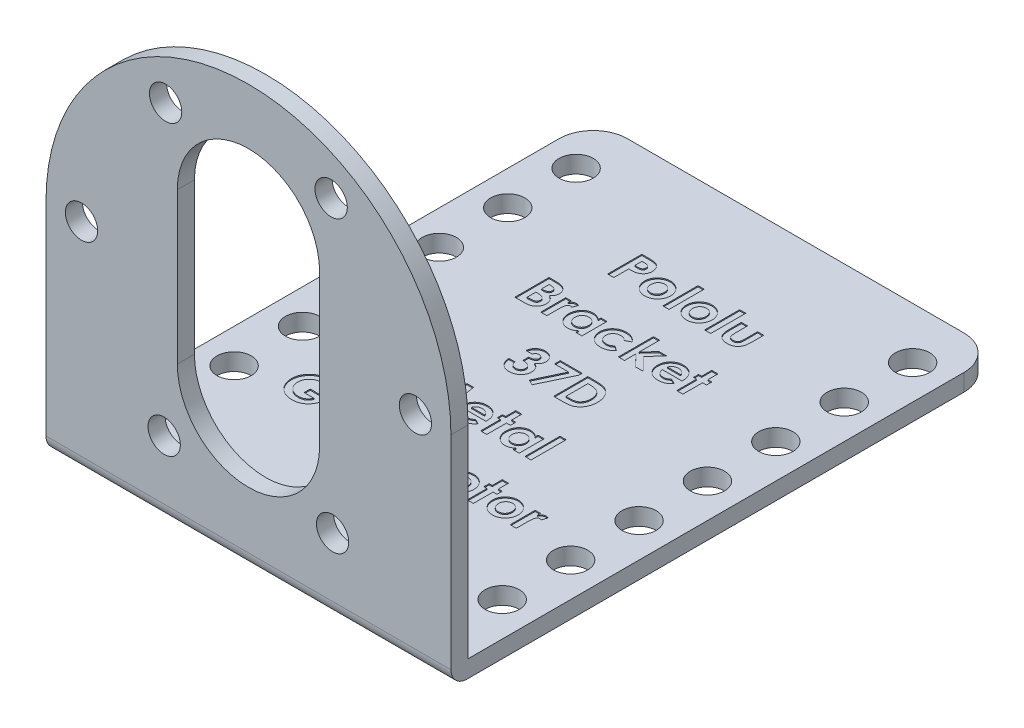
SolidWorks part; units mm, degrees
ref_plane "Plan de face" through (0, 0, 0) normal (0, 0, 1) x (1, 0, 0)
ref_plane "Plan de dessus" through (0, 0, 0) normal (0, 1, 0) x (1, 0, 0)
ref_plane "Plan de droite" through (0, 0, 0) normal (1, 0, 0) x (0, 0, -1)
sketch "Esquisse1" plane through (0, 0, 0) normal (1, 0, 0) x (0, 0, -1)
  line L2 (0, 0) -> (0, 39.18)
  line L3 (0, 39.18) -> (1.59, 39.18)
  line L4 (1.59, 1.59) -> (1.59, 39.18)
  line L5 (0, 0) -> (50.8, 0)
  line L7 (1.59, 1.59) -> (50.8, 1.59)
  line L8 (50.8, 0) -> (50.8, 1.59)
  dimension "D1" = 1.59
  dimension "D2" = 1.59
  dimension "D3" = 39.18
  dimension "D4" = 50.8
extrude "Boss.-Extru.1" add sketch "Esquisse1" along normal blind 37.59
sketch "Esquisse2" plane through (0, 0, 0) normal (0, 0, 1) x (1, 0, 0)
  line L0 (0, 39.18) -> (0, 0) construction
  line L1 (37.59, 39.18) -> (37.59, 0) construction
  line L3 (0, 20.385) -> (0, 39.18)
  line L4 (0, 39.18) -> (37.59, 39.18)
  line L5 (37.59, 39.18) -> (37.59, 20.385)
  line L7 (18.795, 4.885) -> (18.795, 35.885) construction
  line L8 (11.105, 33.8429) -> (26.6049, 6.9964) construction
  line L9 (10.9707, 7.0048) -> (26.4705, 33.8511) construction
  line L10 (3.295, 20.385) -> (34.295, 20.385) construction
  line L13 (18.795, 27.395) -> (18.795, 13.375) construction
  line L14 (25.4, 27.395) -> (25.4, 13.375)
  line L15 (12.19, 27.395) -> (12.19, 13.375)
  arc A0 (0, 20.385) -> (37.59, 20.385) centre (18.795, 20.385) cw
  circle A1 centre (11.105, 33.8429) radius 1.5
  circle A2 centre (26.4705, 33.8511) radius 1.5
  circle A3 centre (26.6049, 6.9964) radius 1.5
  circle A4 centre (10.9707, 7.0048) radius 1.5
  arc A5 (25.4, 27.395) -> (12.19, 27.395) centre (18.795, 27.395) ccw
  arc A6 (12.19, 13.375) -> (25.4, 13.375) centre (18.795, 13.375) ccw
  circle A7 centre (18.795, 20.385) radius 15.5 construction
  circle A8 centre (3.295, 20.385) radius 1.5
  circle A9 centre (34.295, 20.385) radius 1.5
  point P29 (18.795, 20.385)
  line M1 (0, 39.18) -> (0, 0)
  line M3 (37.59, 0) -> (37.59, 39.18)
  line M4 (37.59, 39.18) -> (0, 39.18)
  dimension "D6" = 3
  dimension "D7" = 3
  dimension "D8" = 3
  dimension "D9" = 3
  dimension "D3" = 31
  dimension "D4" = 30
  dimension "D2" = 14.02
  dimension "D5" = 30
  dimension "D10" = 18.795
  dimension "D11" = 13.21
  dimension "D12" = 18.795
extrude "Enlèv. mat.-Extru.1" cut sketch "Esquisse2" against normal blind 38.1 contours A0 L4 M1 | A0 M4 M3 | L15 A6 L14 A5 | A4 | A3 | A2 | A1 | A8 | A9 region at (33.3918, 34.9818, 0) region at (4.1982, 34.9818, 0) region at (18.795, 20.385, 0) region at (11.105, 33.8429, 0) region at (26.4705, 33.8511, 0) region at (26.6049, 6.9964, 0) region at (10.9707, 7.0048, 0) region at (3.295, 20.385, 0) region at (34.295, 20.385, 0)
sketch "Esquisse3" plane through (0, 1.59, 0) normal (0, 1, 0) x (-1, 0, 0)
  line L0 (-3.175, -46.0375) -> (-34.415, -46.0375) construction
  line L1 (-37.59, -50.8) -> (-37.59, -1.59) construction
  line L2 (-37.59, -50.8) -> (0, -50.8) construction
  circle A0 centre (-3.175, -46.0375) radius 1.59
  circle A1 centre (-34.415, -46.0375) radius 1.59
  circle A2 centre (-3.175, -39.6875) radius 1.59
  circle A3 centre (-34.415, -39.6875) radius 1.59
  circle A4 centre (-3.175, -33.3375) radius 1.59
  circle A5 centre (-34.415, -33.3375) radius 1.59
  circle A6 centre (-3.175, -26.9875) radius 1.59
  circle A7 centre (-34.415, -26.9875) radius 1.59
  circle A8 centre (-3.175, -20.6375) radius 1.59
  circle A9 centre (-34.415, -20.6375) radius 1.59
  circle A10 centre (-3.175, -14.2875) radius 1.59
  circle A11 centre (-34.415, -14.2875) radius 1.59
  circle A12 centre (-3.175, -7.9375) radius 1.59
  circle A13 centre (-34.415, -7.9375) radius 1.59
  dimension "D1" = 3.18
  dimension "D2" = 3.18
  dimension "D3" = 31.24
  dimension "D4" = 3.175
  dimension "D6" = 4.7625
  dimension "D5" = 7
extrude "Enlèv. mat.-Extru.2" cut sketch "Esquisse3" against normal blind 10
fillet "Congé1" radius 3.18 2 edges at (37.59, 0.795, -50.8) (0, 0.795, -50.8)
sketch "Esquisse4" plane through (0, 1.59, 0) normal (0, 1, 0) x (1, 0, 0)
  text T0 "<b>     Pololu</b>\r\n<b>   Bracket</b>\r\n<b>       37D </b>\r\n<b>     Metal </b>\r\n<b>Gearmotor </b>" font "Century Gothic" height in points 12
extrude "Enlèv. mat.-Extru.3" cut sketch "Esquisse4" against normal blind 0.1
fillet "Congé2" radius 1.5 1 edges at (18.795, 0, 0)
